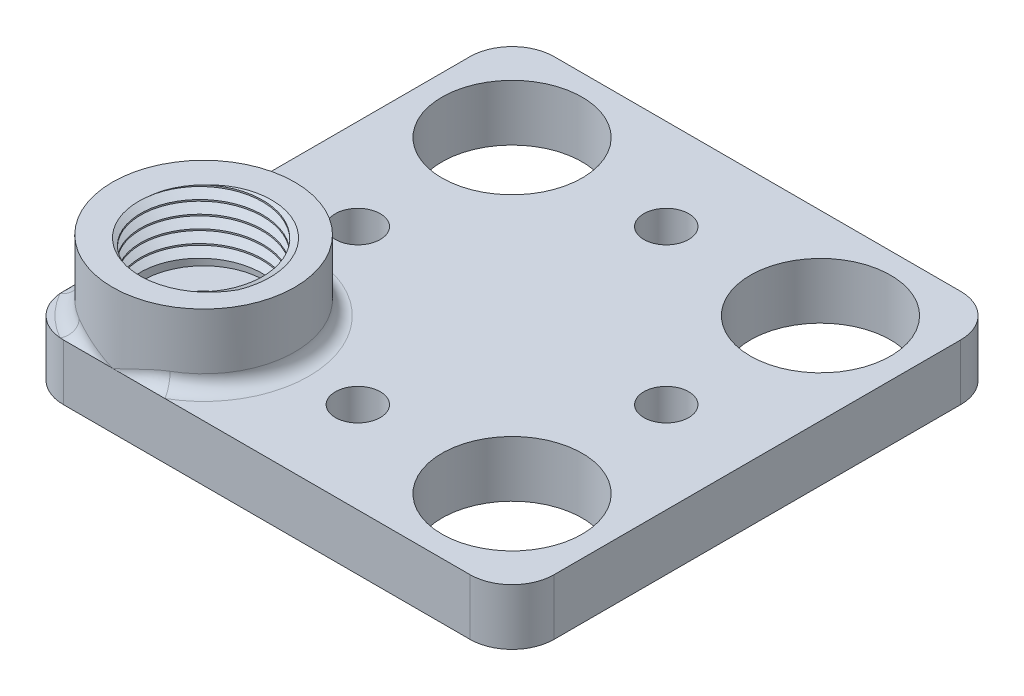
SolidWorks part; units mm, degrees
ref_plane "Front Plane" through (0, 0, 0) normal (0, 0, 1) x (1, 0, 0)
ref_plane "Top Plane" through (0, 0, 0) normal (0, 1, 0) x (1, 0, 0)
ref_plane "Right Plane" through (0, 0, 0) normal (1, 0, 0) x (0, 0, -1)
sketch "Sketch1" plane through (0, 0, 0) normal (0, 1, 0) x (1, 0, 0)
  line L1 (0, 0) -> (35, 0)
  line L2 (0, 0) -> (0, -35)
  line L3 (0, -35) -> (35, -35)
  line L4 (35, 0) -> (35, -35)
  circle A0 centre (28.5, -6.5) radius 5
  circle A1 centre (6.5, -6.5) radius 5
  circle A2 centre (6.5, -28.5) radius 5 construction
  circle A3 centre (28.5, -28.5) radius 5
  circle A4 centre (17.5, -28.5) radius 1.6
  circle A5 centre (17.5, -17.5) radius 3.6254 construction
  circle A6 centre (6.5, -17.5) radius 1.6
  circle A7 centre (17.5, -6.5) radius 1.6
  circle A8 centre (28.5, -17.5) radius 1.6
  circle A9 centre (6.5, -28.5) radius 2.15
  point P26 (17.5, -17.5)
  dimension "D3" = 10
  dimension "D8" = 3.2
  dimension "D12" = 4.3
  dimension "D1" = 35
  dimension "D2" = 35
  dimension "D4" = 6.5
  dimension "D5" = 6.5
  dimension "D9" = 6.5
  dimension "D10" = 17.5
  dimension "D6" = 2
  dimension "D7" = 2
  dimension "D11" = 4
extrude "Boss-Extrude1" add sketch "Sketch1" along normal blind 4
sketch "Sketch4" plane through (0, 4, 0) normal (0, 1, 0) x (1, 0, 0)
  circle A0 centre (6.5, -28.5) radius 4.35
  circle A1 centre (6.5, -28.5) radius 6.5
  dimension "D1" = 8.7
  dimension "D2" = 13
extrude "Boss-Extrude3" add sketch "Sketch4" along normal blind 5
fillet "Fillet2" radius 1 2 edges at (11.0962, 4, 23.9038) (1.9038, 4, 33.0962)
fillet "Fillet3" radius 3 4 edges at (0, 2, 35) (0, 2, 0) (35, 2, 0) (35, 2, 35)
sketch "Sketch5" plane through (0, 9, 0) normal (0, 1, 0) x (1, 0, 0)
  circle A0 centre (6.5, -28.5) radius 4.35
curve "Helix/Spiral1" pitch 0.907 height 4.535 radius 4.35 centre (6.5, 9, 28.5) axis (0, -1, 0) start towards (0, 0, 1)
ref_plane "Plane1" through (6.5, 0, 0) normal (1, 0, 0) x (0, 0, -1)
sketch "Sketch7" plane through (6.5, 0, 0) normal (1, 0, 0) x (0, 0, -1)
  line L0 (-32.75, 4.7544) -> (-32.75, 3.8484)
  line L1 (-32.75, 3.8484) -> (-33.6202, 4.3014)
  line L2 (-33.6202, 4.3014) -> (-32.75, 4.7544)
  line L4 (-35, 4) -> (-35, 0) construction
  dimension "D1" = 0.906
  dimension "D2" = 55
  dimension "D3" = 62.5
  dimension "D4" = 2.25
sweep "Cut-Sweep1" cut profiles "Sketch7" path "Helix/Spiral1" align with end faces yes
equation "\"D4@Sketch1\"=6.5"
equation "\"D9@Sketch1\"=\"D5@Sketch1\""
equation "\"D10@Sketch1\"=\"D1@Sketch1\"/2"
equation "\"D3@Sketch7\"=90-55/2"
